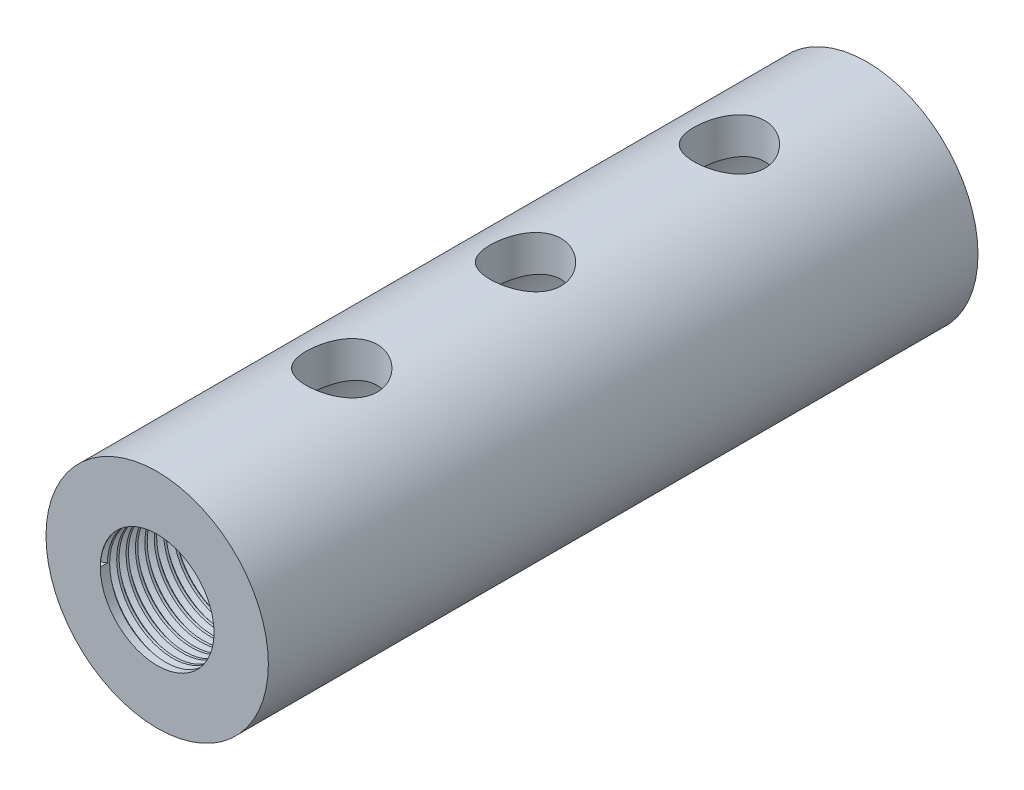
SolidWorks part; units mm, degrees
material "Acrylic (Medium-high impact)"
ref_plane "Front Plane" through (0, 0, 0) normal (0, 0, 1) x (1, 0, 0)
ref_plane "Top Plane" through (0, 0, 0) normal (0, 1, 0) x (1, 0, 0)
ref_plane "Right Plane" through (0, 0, 0) normal (1, 0, 0) x (0, 0, -1)
sketch "Sketch1" plane through (0, 0, 0) normal (0, 0, 1) x (1, 0, 0)
  circle A0 centre (0, 0) radius 4.7
extrude "Boss-Extrude1" add sketch "Sketch1" along normal blind 30 contours A0
sketch "Sketch2" plane through (0, 0, 30) normal (0, 0, 1) x (1, 0, 0)
  circle A0 centre (0, 0) radius 2.405
sketch "Sketch4" plane through (0, 0, 0) normal (0, 1, 0) x (1, 0, 0)
  circle A0 centre (0, -14.4286) radius 1.5
extrude "Cut-Extrude4" cut sketch "Sketch4" against normal through all both and the other way through all
sketch "Sketch5" plane through (0, 0, 0) normal (0, 1, 0) x (1, 0, 0)
  circle A0 centre (0, -22.1973) radius 1.5
sketch "Sketch6" plane through (0, 0, 0) normal (0, 1, 0) x (1, 0, 0)
  circle A0 centre (0, -5.8101) radius 1.5
extrude "Cut-Extrude6" cut sketch "Sketch6" against normal through all both and the other way through all
extrude "Cut-Extrude8" cut sketch "Sketch2" against normal blind 6
sketch "Sketch7" plane through (0, 0, 24) normal (0, 0, 1) x (1, 0, 0)
  circle A1 centre (0, 0) radius 3.2
extrude "Cut-Extrude9" cut sketch "Sketch7" against normal through all
extrude "Cut-Extrude10" cut sketch "Sketch5" against normal through all both and the other way through all contours A0
thread "Thread1" pitch 0.3969 method cut profile "Thread Profile1" start angle 0, offset 0, length 5, pitch 0.3969, diameter 4.81
ref_plane "Plane1" through (-2.405, 0, 30) normal (0, -1, 0) x (-1, 0, 0)
sketch "Thread Profile1" plane through (-2.405, 0, 30) normal (0, -1, 0) x (-1, 0, 0)
  line L0 (0, 0) -> (0, 0.3969) construction
  line L1 (0, 0) -> (0.2148, 0.124)
  line L2 (0.2148, 0.124) -> (0.2148, 0.1736)
  line L3 (0.2148, 0.1736) -> (0, 0.2977)
  line L4 (0.2148, 0.1488) -> (0, 0.1488) construction
  line L11 (0, 0) -> (0, 0.2977)
  point P2 (0, 0)
  dimension "Pitch" = 0.3969
  dimension "Profile_Angle" = 60
  dimension "Profile_Land" = 0.0496
  dimension "Profile_Height" = 0.2148
